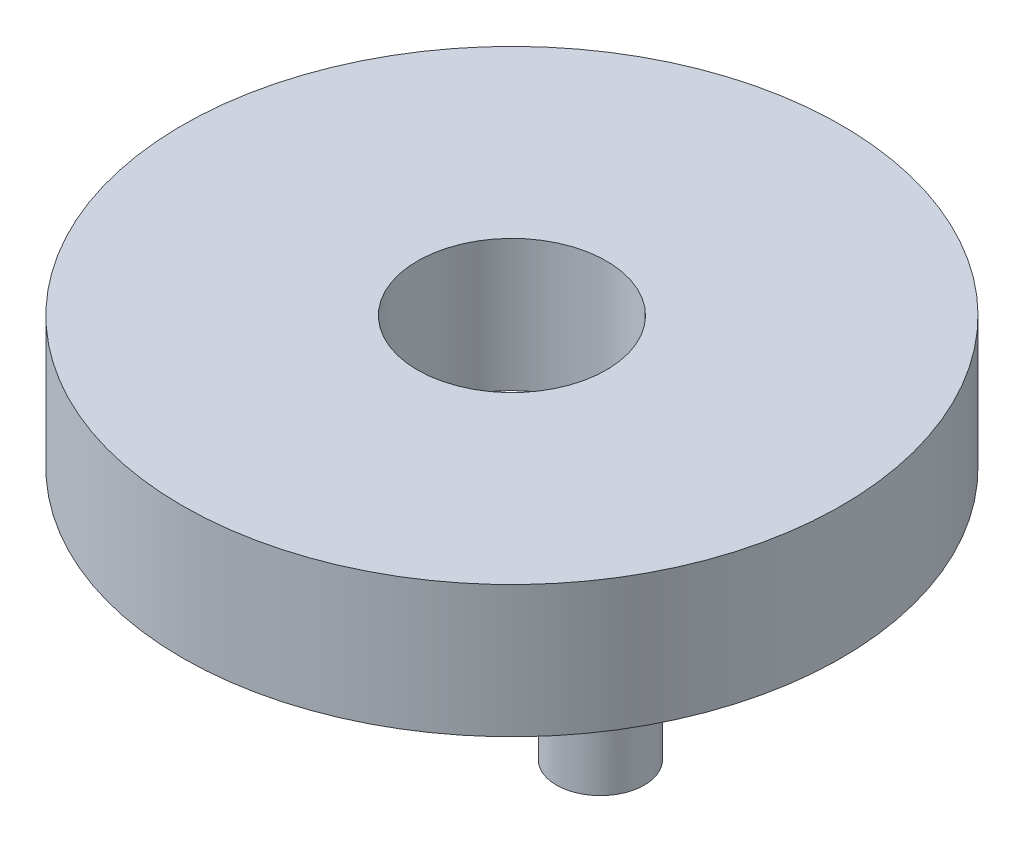
SolidWorks part; units mm, degrees
material "Onyx w/ CF"
ref_plane "Front Plane" through (0, 0, 0) normal (0, 0, 1) x (1, 0, 0)
ref_plane "Top Plane" through (0, 0, 0) normal (0, 1, 0) x (1, 0, 0)
ref_plane "Right Plane" through (0, 0, 0) normal (1, 0, 0) x (0, 0, -1)
sketch "Sketch1" plane through (0, 0, 0) normal (0, 1, 0) x (1, 0, 0)
  circle A0 centre (0, 0) radius 7.5
  dimension "D1" = 15
extrude "Boss-Extrude1" add sketch "Sketch1" along normal blind 3
hole_wizard "M4 Clearance Hole1" positions "Sketch2" profile "Sketch3" hole size "M4" standard "ANSI Metric" end condition up to next
sketch "Sketch2" plane through (0, 3, 0) normal (0, 1, 0) x (1, 0, 0)
  point P0 (0, 0)
sketch "Sketch3" plane through (0, 3, 0) normal (1, 0, 0) x (0, 0, 1)
  line L0 (0, 0) -> (0, 3)
  line L1 (0, 3) -> (2.15, 3)
  line L2 (2.15, 3) -> (2.15, 0)
  line L5 (2.15, 0) -> (0, 0)
  line L11 (0, -6.35) -> (0, 107.95) construction
  dimension "Thru Hole Dia." = 4.3
  dimension "Thru Hole Depth" = 3
sketch "Sketch4" plane through (0, 0, 0) normal (0, -1, 0) x (1, 0, 0)
  line L0 (0, 0) -> (4.7631, 2.75) construction
  line L1 (0, 0) -> (-4.7631, 2.75) construction
  circle A0 centre (0, -5.5) radius 1
  circle A1 centre (4.7631, 2.75) radius 1
  circle A2 centre (-4.7631, 2.75) radius 1
  circle A3 centre (0, 0) radius 5.5 construction
  dimension "D1" = 2
  dimension "D3" = 11
  dimension "D2" = 120
extrude "Boss-Extrude2" add sketch "Sketch4" along normal blind 2
